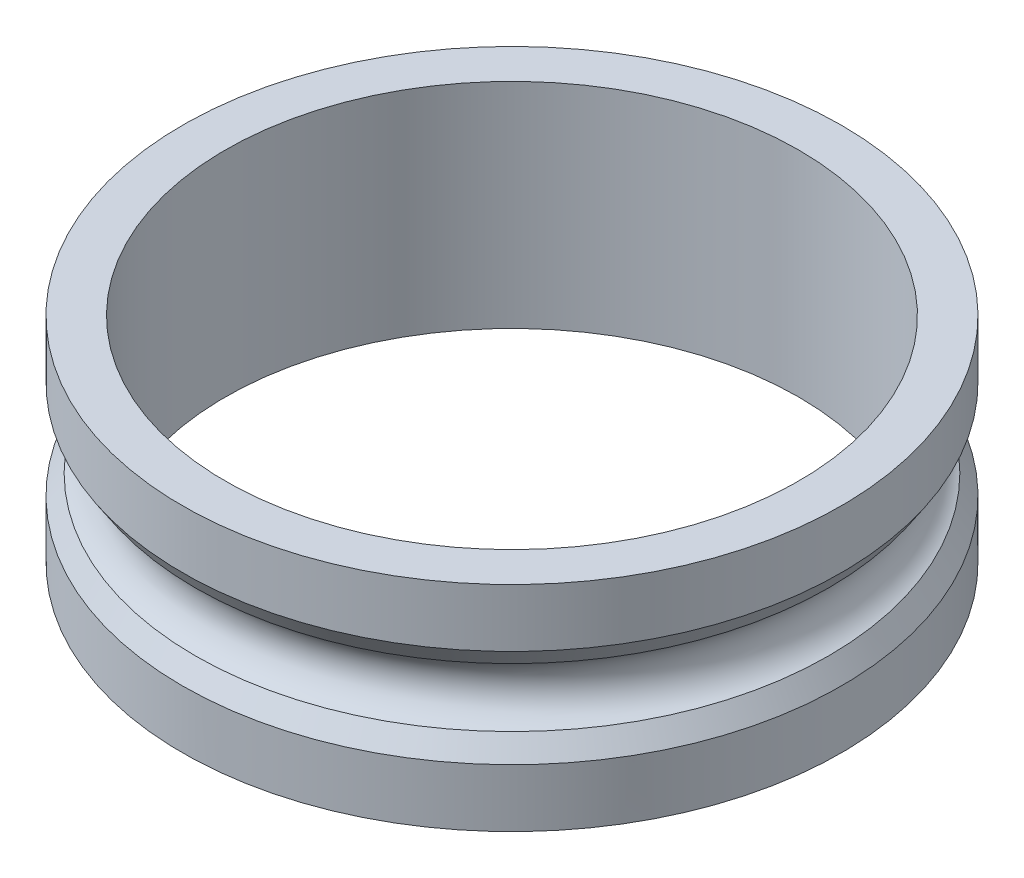
SolidWorks part; units mm, degrees
ref_plane "Front Plane" through (0, 0, 0) normal (0, 0, 1) x (1, 0, 0)
ref_plane "Top Plane" through (0, 0, 0) normal (0, 1, 0) x (1, 0, 0)
ref_plane "Right Plane" through (0, 0, 0) normal (1, 0, 0) x (0, 0, -1)
sketch "Sketch1" plane through (0, 0, 0) normal (0, 0, 1) x (1, 0, 0)
  line L0 (6.7, -2.5) -> (6.7, 2.5)
  line L1 (6.7, 2.5) -> (7.7, 2.5)
  line L2 (7.7, 2.5) -> (7.7, 0.75)
  line L3 (6.7, -2.5) -> (7.7, -2.5)
  line L4 (7.7, -2.5) -> (7.7, -0.75)
  line L5 (0, 0) -> (0, 5.1578) construction
  arc A0 (7.7, -0.75) -> (7.7, 0.75) centre (7.7, 0) cw
  point P8 (6.7, 0)
  dimension "D1" = 0.75
  dimension "D2" = 5
  dimension "D3" = 1
  dimension "D4" = 6.7
revolve "Revolve1" add sketch "Sketch1" angle 360 about L5
chamfer "Chamfer1" distance 0.5 angle 45 2 edges at (0, -0.75, -7.7) (0, 0.75, -7.7)
